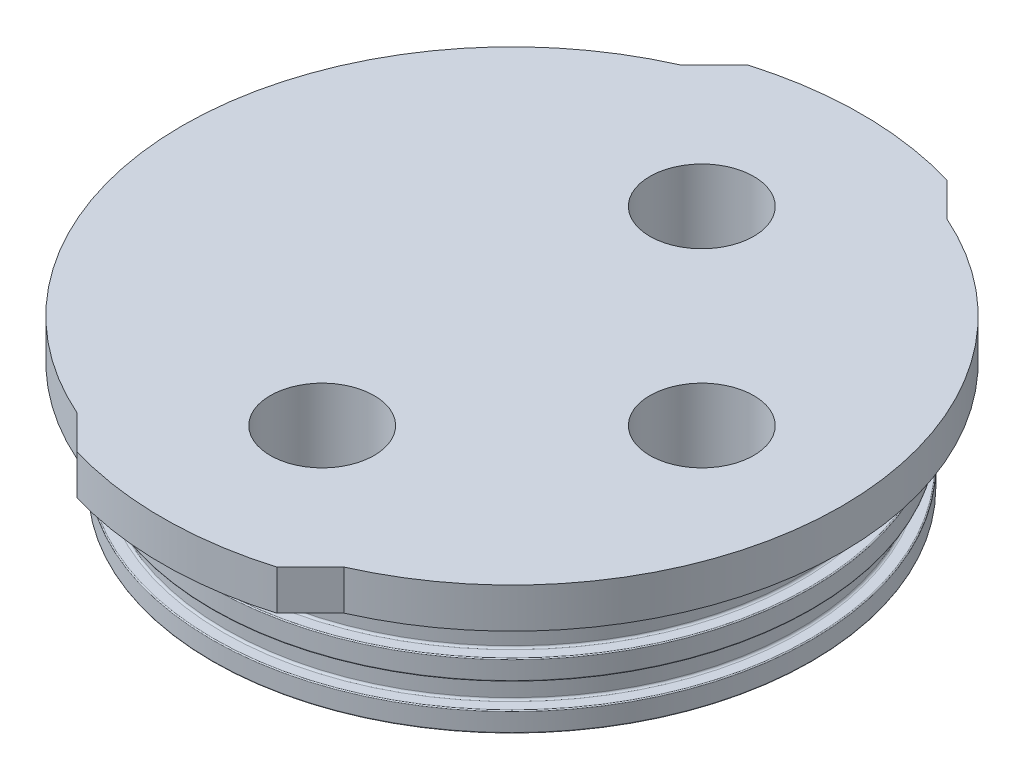
SolidWorks part; units mm, degrees
ref_plane "Piano frontale" through (0, 0, 0) normal (0, 0, 1) x (1, 0, 0)
ref_plane "Piano superiore" through (0, 0, 0) normal (0, 1, 0) x (1, 0, 0)
ref_plane "Piano destro" through (0, 0, 0) normal (1, 0, 0) x (0, 0, -1)
sketch "Schizzo3" plane through (0, 0, 0) normal (0, 0, 1) x (1, 0, 0)
  line L0 (0, 0) -> (0, 62.9272) construction
  line L1 (0, 15) -> (-33, 15)
  line L2 (-33, 15) -> (-33, 11)
  line L3 (-33, 11) -> (-30, 11)
  line L4 (-30, 11) -> (-30, 9)
  line L5 (-30, 9) -> (-28.7, 9)
  line L6 (-28.7, 9) -> (-28.7, 6.5)
  line L7 (-28.7, 6.5) -> (-30, 6.5)
  line L8 (-30, 6.5) -> (-30, 4.5)
  line L9 (-30, 4.5) -> (-28.7, 4.5)
  line L10 (-28.7, 4.5) -> (-28.7, 2)
  line L11 (-28.7, 2) -> (-30, 2)
  line L12 (-30, 2) -> (-30, 0)
  line L13 (-30, 0) -> (0, 0)
  line L14 (0, 0) -> (0, 15)
  dimension "D1" = 60
  dimension "D2" = 66
  dimension "D3" = 1.3
  dimension "D4" = 2.5
  dimension "D5" = 2
  dimension "D6" = 4
  dimension "D7" = 57.4
  dimension "D8" = 2
  dimension "D9" = 2
  dimension "D10" = 11
revolve "Rivoluzione1" add sketch "Schizzo3" angle 360 about L0
sketch "Schizzo4" plane through (0, 0, 0) normal (1, 0, 0) x (0, 0, -1)
  line L0 (-12, 15) -> (-12, 0) construction
  line L1 (33, 15) -> (-33, 15) construction
  line L2 (-30, 0) -> (30, 0) construction
  line L3 (-12, 0) -> (-19.8, 0)
  line L4 (-19.8, 0) -> (-22.4449, 15)
  line L5 (-22.4449, 15) -> (-12, 15)
  line L6 (-12, 15) -> (-12, 0)
  dimension "D1" = 7.8
  dimension "D2" = 10
  dimension "D3" = 12
revolve "Taglia-Rivoluzione1" [suppressed] cut sketch "Schizzo4" angle 360 about L0
sketch "Schizzo5" plane through (0, 0, 0) normal (1, 0, 0) x (0, 0, -1)
  line L0 (19, 23.4828) -> (19, -5.9469) construction
  line L1 (33, 15) -> (-33, 15) construction
  line L2 (19, 15) -> (24.2, 15)
  line L3 (19, 15) -> (19, 0)
  line L4 (19, 0) -> (24.2, 0)
  line L5 (24.2, 15) -> (24.2, 0)
  line L6 (-30, 0) -> (30, 0) construction
  dimension "D1" = 10.4
  dimension "D2" = 19
  dimension "D3" = 11
revolve "Taglia-Rivoluzione2" cut sketch "Schizzo5" angle 360 about L0
chamfer "Smusso1" [suppressed] distance 1 angle 45
sketch "Schizzo6" plane through (0, 15, 0) normal (0, 1, 0) x (1, 0, 0)
  circle A0 centre (0, 0) radius 18
  dimension "D1" = 36
extrude "Taglio-Estrusione1" [suppressed] cut sketch "Schizzo6" against normal through all
mirror "Specchia1" about plane through (0, 0, 0) normal (0, 0, 1) of "Smusso1", "Taglia-Rivoluzione2"
ref_axis "Asse1" through (0, 15, 0) along (0, -1, 0)
pattern_circular "RipetizioneCircolare1" count 2 every 90 about axis through (0, 15, 0) along (0, -1, 0) of "Taglia-Rivoluzione2", "Smusso1"
sketch "Schizzo7" plane through (0, 15, 0) normal (0, 1, 0) x (1, 0, 0)
  line L0 (0, 0) -> (33, 0) construction
  line L1 (-10, 33.541) -> (-13.3714, 30.1696)
  line L2 (0, 35) -> (0, 33) construction
  line L3 (10, 33.541) -> (13.3714, 30.1696)
  circle A0 centre (0, 0) radius 33 construction
  circle A1 centre (0, 0) radius 35 construction
  arc A2 (-10, 33.541) -> (0, 35) centre (0, 0) cw
  arc A3 (13.3714, 30.1696) -> (-13.3714, 30.1696) centre (0, 0) ccw
  arc A4 (10, 33.541) -> (0, 35) centre (0, 0) ccw
  dimension "D1" = 70
  dimension "D2" = 45
  dimension "D3" = 10
extrude "Estrusione-Estrusione1" add sketch "Schizzo7" against normal up to surface (4 mm away) up to face at (0, 11, -30)
pattern_circular "RipetizioneCircolare2" count 2 over 360 about axis through (0, 0, 0) along (0, -1, 0) of "Estrusione-Estrusione1"
fillet "Raccordo1" radius 0.1 5 edges at (0, 9, -30) (0, 6.5, -30) (0, 4.5, -30) (0, 2, -30) (0, 0, -30)
fillet "Raccordo2" radius 0.2 4 edges at (0, 9, -28.7) (0, 6.5, -28.7) (0, 4.5, -28.7) (0, 2, -28.7)
